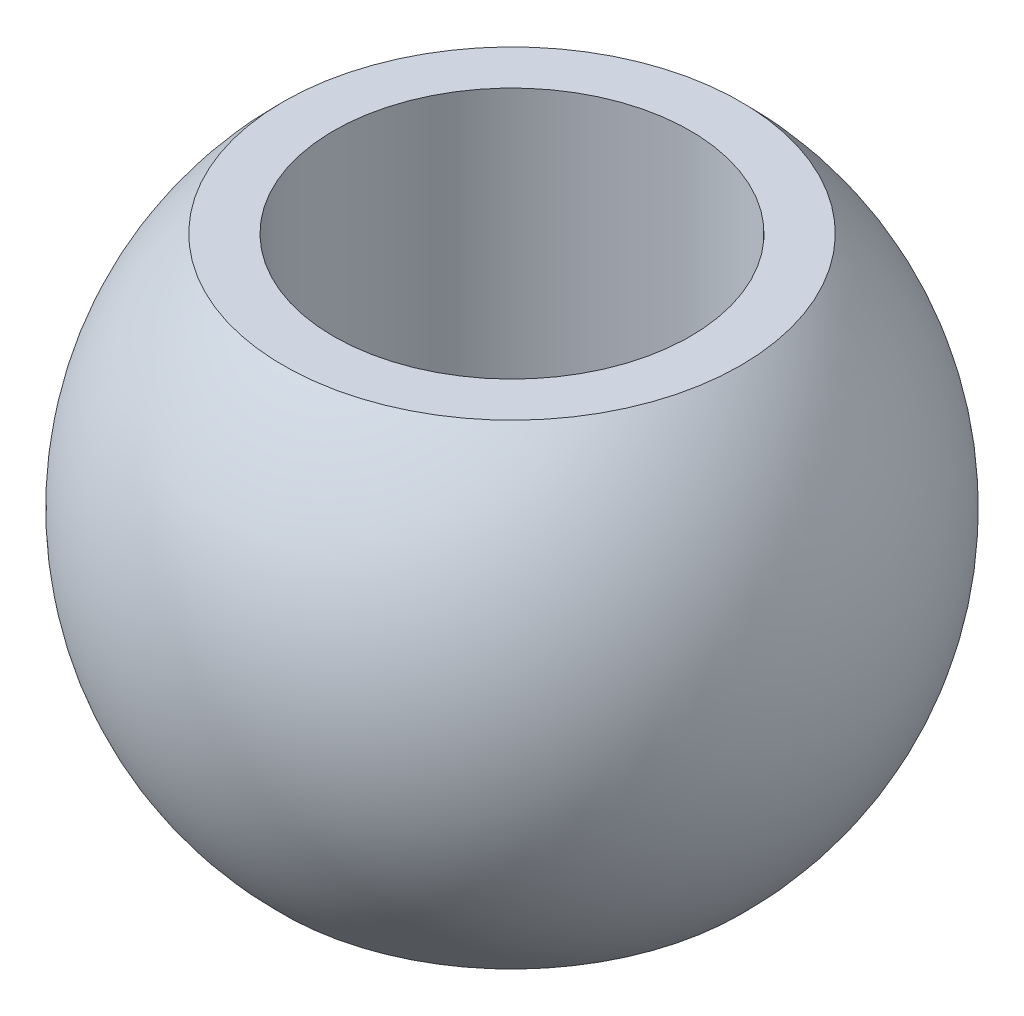
SolidWorks part; units mm, degrees
material "iglidur W300"
ref_plane "Płaszczyzna przednia" through (0, 0, 0) normal (0, 0, 1) x (1, 0, 0)
ref_plane "Płaszczyzna górna" through (0, 0, 0) normal (0, 1, 0) x (1, 0, 0)
ref_plane "Płaszczyzna prawa" through (0, 0, 0) normal (1, 0, 0) x (0, 0, -1)
sketch "Szkic1" plane through (0, 0, 0) normal (0, 0, 1) x (1, 0, 0)
  line L0 (-7.6948, 8) -> (-6, 8)
  line L1 (-6, 8) -> (-6, -8)
  line L2 (-6, -8) -> (-7.6948, -8)
  line L4 (0, 8) -> (0, 0) construction
  arc A0 (-7.6948, 8) -> (-7.6948, -8) centre (0, 0) ccw
  dimension "D1" = 22.2
  dimension "D2" = 6
  dimension "D3" = 8
  dimension "D4" = 8
revolve "Obrót1" add sketch "Szkic1" angle 360 about L4
